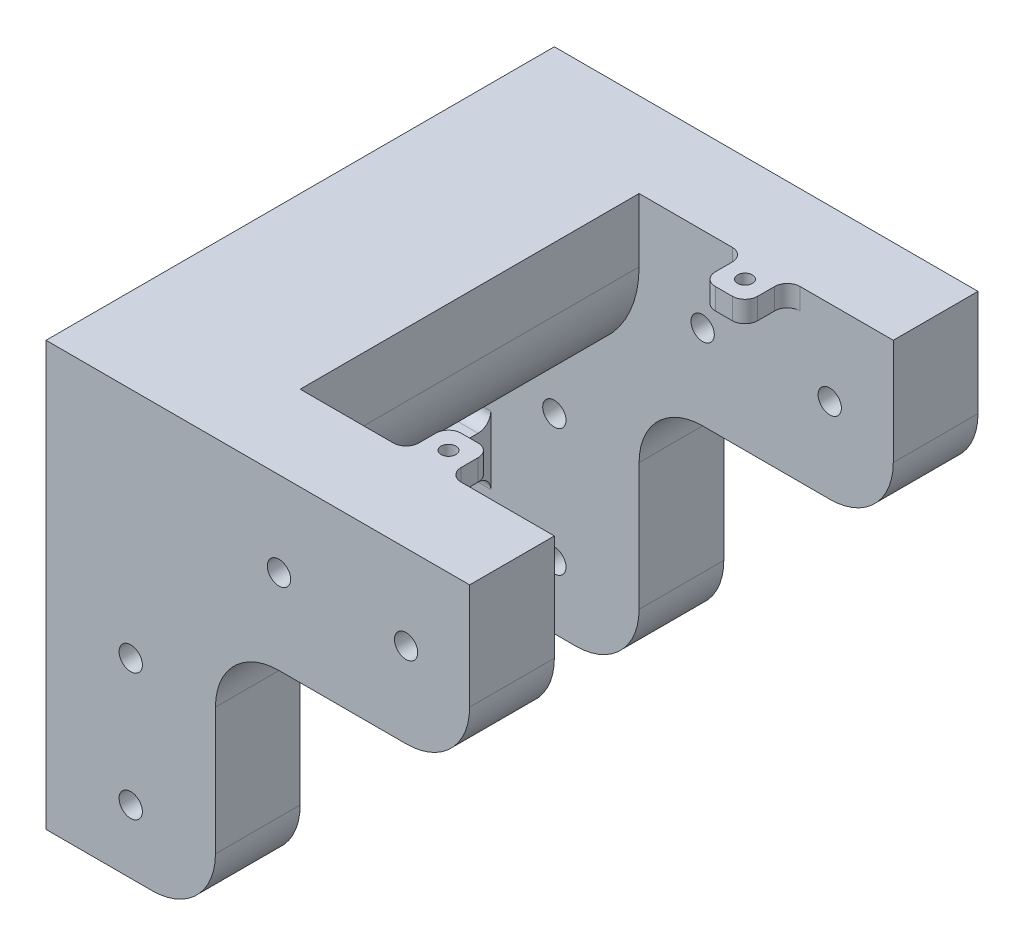
SolidWorks part; units mm, degrees
ref_plane "Front Plane" through (0, 0, 0) normal (0, 0, 1) x (1, 0, 0)
ref_plane "Top Plane" through (0, 0, 0) normal (0, 1, 0) x (1, 0, 0)
ref_plane "Right Plane" through (0, 0, 0) normal (1, 0, 0) x (0, 0, -1)
sketch "Sketch1" plane through (0, 0, 0) normal (0, 0, 1) x (1, 0, 0)
  line L0 (100, 380) -> (100, 340)
  line L1 (0, 380) -> (100, 380)
  line L2 (0, 380) -> (0, 280)
  line L5 (0, 280) -> (40, 280)
  line L6 (100, 340) -> (40, 340)
  line L7 (40, 280) -> (40, 340)
  dimension "D1" = 100
  dimension "D2" = 100
  dimension "D3" = 40
  dimension "D4" = 40
extrude "Boss-Extrude1" add sketch "Sketch1" along normal blind 20
sketch "Sketch2" plane through (0, 0, 20) normal (0, 0, 1) x (1, 0, 0)
  line L1 (0, 380) -> (40, 380)
  line L2 (0, 380) -> (0, 340)
  line L3 (0, 340) -> (40, 340)
  line L4 (40, 380) -> (40, 340)
extrude "Boss-Extrude2" add sketch "Sketch2" along normal blind 80
sketch "Sketch3" plane through (0, 0, 100) normal (0, 0, 1) x (1, 0, 0)
  line L1 (0, 380) -> (100, 380)
  line L2 (0, 380) -> (0, 340)
  line L3 (0, 340) -> (100, 340)
  line L4 (100, 380) -> (100, 340)
  line L5 (0, 380) -> (40, 380)
  line L6 (0, 380) -> (0, 280)
  line L7 (0, 280) -> (40, 280)
  line L8 (40, 380) -> (40, 280)
  line M1 (0, 380) -> (0, 340)
  line M2 (0, 340) -> (40, 340)
  line M3 (40, 340) -> (40, 380)
  line M4 (40, 380) -> (0, 380)
extrude "Boss-Extrude3" add sketch "Sketch3" along normal blind 20 contours L8 L6 L7 M2 | M4 M1 M2 M3 | L4 L1 L3 M3 region at (20, 360, 100) region at (70, 360, 100) region at (20, 310, 100)
sketch "Sketch5" plane through (0, 0, 120) normal (0, 0, 1) x (1, 0, 0)
  line L0 (100, 360) -> (70, 360)
  line L1 (100, 380) -> (100, 340) construction
  line L2 (40, 340) -> (40, 360)
  line L3 (40, 340) -> (0, 340)
  line L4 (0, 380) -> (0, 280) construction
  line L5 (20, 310) -> (20, 280)
  line L6 (0, 280) -> (40, 280) construction
  line L7 (70, 360) -> (70, 353.3288)
  line L8 (20, 310) -> (28.3715, 310)
  circle A0 centre (85, 360) radius 2.75
  circle A1 centre (55, 360) radius 2.75
  circle A2 centre (20, 295) radius 2.75
  circle A3 centre (20, 325) radius 2.75
  dimension "D1" = 5.5
  dimension "D2" = 5.5
extrude "Cut-Extrude1" cut sketch "Sketch5" against normal blind 167 contours A1 | L0 A0 | L0 A0 | A3 | L5 A2 | L5 A2 region at (85, 358.8329, 120) region at (85, 361.1671, 120) region at (21.1671, 295, 120) region at (18.8329, 295, 120) region at (55, 360, 120) region at (20, 325, 120)
fillet "Fillet1" radius 25 1 edges at (40, 340, 60)
fillet "Fillet2" radius 15 6 edges at (40, 340, 10) (40, 280, 10) (100, 340, 10) (100, 340, 110) (40, 280, 110) (40, 340, 110)
sketch "Sketch6" plane through (0, 0, 20) normal (0, 0, 1) x (1, 0, 0)
  line L0 (0, 340) -> (0, 280)
  line L1 (0, 310) -> (5, 310)
  line L2 (0, 305) -> (5, 305)
  line L3 (0, 315) -> (5, 315)
  line L4 (5, 315) -> (5, 305)
  line L5 (0, 315) -> (0, 305)
  line L6 (32.6777, 347.3223) -> (37.1401, 342.8599)
  line L7 (65, 380) -> (75, 380)
  line L8 (65, 375) -> (75, 375)
  line L9 (65, 380) -> (65, 375)
  line L10 (75, 380) -> (75, 375)
  line L11 (70, 380) -> (70, 375)
  arc A0 (15, 340) -> (40, 365) centre (15, 365) ccw construction
  dimension "D1" = 5
  dimension "D2" = 5
  dimension "D3" = 5
extrude "Boss-Extrude4" add sketch "Sketch6" along normal blind 10 contours L4 L3 L0 L1 | L4 L1 L0 L2 | L11 L7 L9 L8 | L11 L8 L10 region at (2.5, 312.5, 20) region at (2.5, 307.5, 20) region at (67.5, 377.5, 20) region at (72.5, 377.5, 20)
sketch "Sketch7" plane through (0, 375, 0) normal (0, -1, 0) x (1, 0, 0)
  line L0 (70, 30) -> (70, 20)
  line L1 (65, 30) -> (75, 30) construction
  line L2 (55, 20) -> (85, 20) construction
  circle A0 centre (70, 25) radius 1.75
  dimension "D1" = 3.5
extrude "Cut-Extrude2" cut sketch "Sketch7" against normal blind 10 contours L0 A0 | L0 A0 region at (70.7427, 375, 25) region at (69.2573, 375, 25)
sketch "Sketch8" plane through (5, 0, 0) normal (1, 0, 0) x (0, 0, -1)
  line L0 (-30, 310) -> (-20, 310)
  line L1 (-30, 315) -> (-30, 305) construction
  line L2 (-20, 295) -> (-20, 325) construction
  circle A0 centre (-25, 310) radius 1.75
  dimension "D1" = 3.5
extrude "Cut-Extrude3" cut sketch "Sketch8" against normal blind 10 contours L0 A0 | L0 A0 region at (5, 310.7427, 25) region at (5, 309.2573, 25)
sketch "Sketch9" plane through (0, 0, 100) normal (0, 0, -1) x (-1, 0, 0)
  line L0 (-65, 375) -> (-75, 375) construction
  line L1 (-75, 375) -> (-75, 380) construction
  line L2 (-75, 380) -> (-65, 380) construction
  line L3 (-65, 380) -> (-65, 375) construction
  line L4 (-5, 305) -> (-5, 315) construction
  line L5 (-5, 315) -> (0, 315) construction
  line L6 (0, 315) -> (0, 305) construction
  line L7 (0, 305) -> (-5, 305) construction
  line L8 (-65, 375) -> (-75, 375)
  line L9 (-75, 375) -> (-75, 380)
  line L10 (-75, 380) -> (-65, 380)
  line L11 (-65, 380) -> (-65, 375)
  line L12 (-5, 305) -> (-5, 315)
  line L13 (-5, 315) -> (0, 315)
  line L14 (0, 315) -> (0, 305)
  line L15 (0, 305) -> (-5, 305)
extrude "Boss-Extrude5" add sketch "Sketch9" along normal blind 10
sketch "Sketch10" plane through (5, 0, 0) normal (1, 0, 0) x (0, 0, -1)
  line L0 (-90, 310) -> (-100, 310)
  line L1 (-90, 315) -> (-90, 305) construction
  line L2 (-100, 325) -> (-100, 295) construction
  circle A0 centre (-95, 310) radius 1.75
  dimension "D1" = 3.5
extrude "Cut-Extrude4" cut sketch "Sketch10" against normal blind 10 contours L0 A0 | L0 A0 region at (5, 309.2573, 95) region at (5, 310.7427, 95)
sketch "Sketch11" plane through (0, 375, 0) normal (0, -1, 0) x (1, 0, 0)
  line L0 (70, 100) -> (70, 90)
  line L1 (55, 100) -> (85, 100) construction
  line L2 (75, 90) -> (65, 90) construction
  circle A0 centre (70, 95) radius 1.75
  dimension "D1" = 3.5
extrude "Cut-Extrude5" cut sketch "Sketch11" against normal blind 10 contours L0 A0 | L0 A0 region at (70.7427, 375, 95) region at (69.2573, 375, 95)
fillet "Fillet4" radius 3 16 edges at (75, 377.5, 100) (65, 377.5, 100) (65, 377.5, 90) (75, 377.5, 90) (65, 377.5, 20) (75, 377.5, 20) (65, 377.5, 30) (75, 377.5, 30) (2.5, 315, 20) (2.5, 315, 30) (2.5, 305, 20) (2.5, 305, 30) (2.5, 315, 100) (2.5, 315, 90) (2.5, 305, 100) (2.5, 305, 90)
